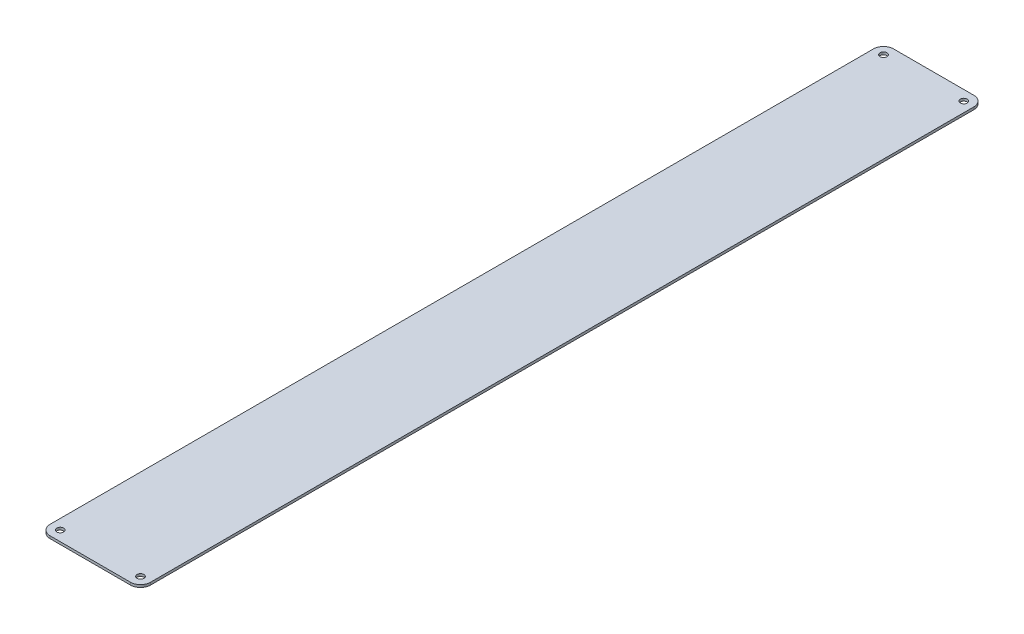
SolidWorks part; units mm, degrees
ref_plane "Front Plane" through (0, 0, 0) normal (0, 0, 1) x (1, 0, 0)
ref_plane "Top Plane" through (0, 0, 0) normal (0, 1, 0) x (1, 0, 0)
ref_plane "Right Plane" through (0, 0, 0) normal (1, 0, 0) x (0, 0, -1)
sketch "Sketch1" plane through (0, 0, 0) normal (0, 1, 0) x (1, 0, 0)
  line L1 (6.35, 0) -> (57.15, 0)
  line L2 (0, 6.35) -> (0, 527.05)
  line L3 (6.35, 533.4) -> (57.15, 533.4)
  line L4 (63.5, 6.35) -> (63.5, 527.05)
  circle A0 centre (57.15, 527.05) radius 2.1828
  circle A1 centre (6.35, 527.05) radius 2.1828
  arc A2 (6.35, 533.4) -> (0, 527.05) centre (6.35, 527.05) ccw
  arc A3 (63.5, 527.05) -> (57.15, 533.4) centre (57.15, 527.05) ccw
  circle A4 centre (6.35, 6.35) radius 2.1828
  circle A5 centre (57.15, 6.35) radius 2.1828
  arc A6 (6.35, 0) -> (0, 6.35) centre (6.35, 6.35) cw
  arc A7 (63.5, 6.35) -> (57.15, 0) centre (57.15, 6.35) cw
  point P19 (0, 0)
  dimension "D7" = 4.3656
  dimension "D8" = 4.3656
  dimension "D9" = 6.35
  dimension "D10" = 6.35
  dimension "D15" = 4.3656
  dimension "D16" = 4.3656
  dimension "D17" = 6.35
  dimension "D18" = 6.35
  dimension "D1" = 63.5
  dimension "D2" = 533.4
  dimension "D3" = 6.35
  dimension "D4" = 6.35
  dimension "D5" = 6.35
  dimension "D6" = 6.35
  dimension "D11" = 6.35
  dimension "D12" = 6.35
  dimension "D13" = 6.35
  dimension "D14" = 6.35
extrude "Boss-Extrude1" add sketch "Sketch1" along normal mid plane 1.5875
